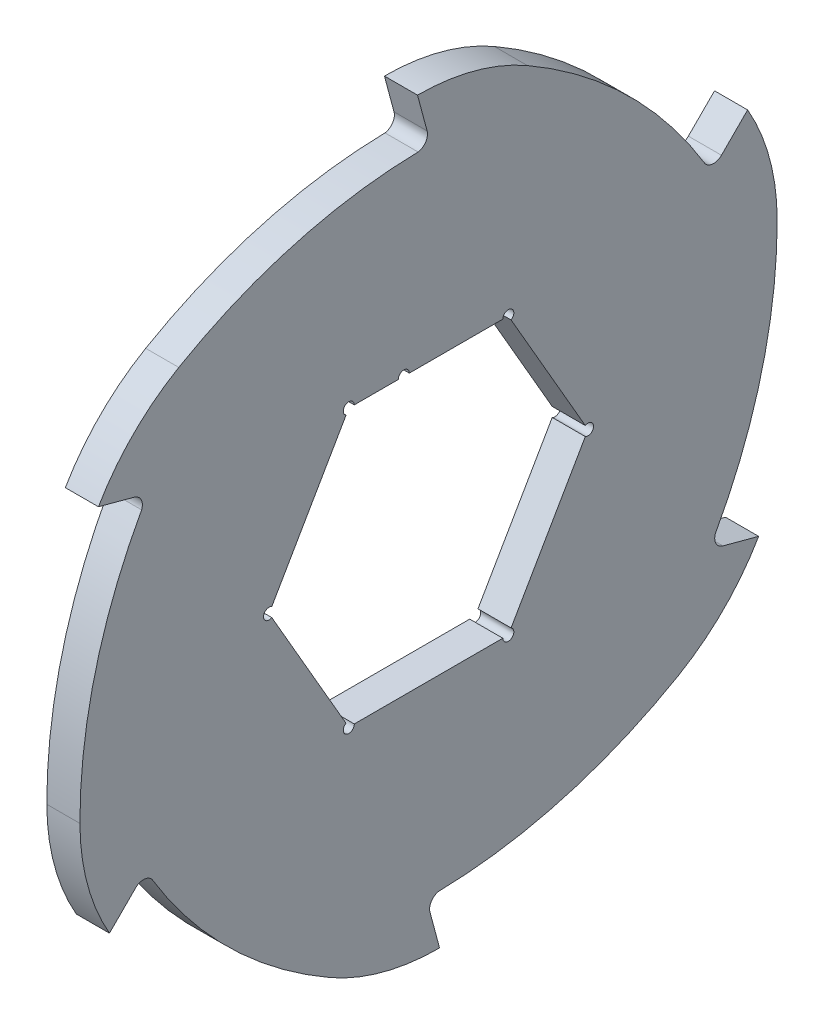
SolidWorks part; units mm, degrees
note: '?' marks a value the reader was unsure of.
material "1.0037 (S235JR)"
ref_plane "Alzado" through (0, 0, 0) normal (0, 0, 1) x (1, 0, 0)
ref_plane "Planta" through (0, 0, 0) normal (0, 1, 0) x (1, 0, 0)
ref_plane "Vista lateral" through (0, 0, 0) normal (1, 0, 0) x (0, 0, -1)
sketch "Sketch1" plane through (0, 0, 0) normal (1, 0, 0) x (0, 0, -1)
  line L0 (-56.6126, 0) -> (65.57, 0) construction
  line L1 (14.4626, 25.05) -> (-14.4626, 25.05)
  line L2 (-14.4626, 25.05) -> (-28.9252, 0)
  line L3 (-28.9252, 0) -> (-14.4626, -25.05)
  line L4 (-14.4626, -25.05) -> (14.4626, -25.05)
  line L5 (14.4626, -25.05) -> (28.9252, 0)
  line L6 (28.9252, 0) -> (14.4626, 25.05)
  circle A0 centre (0, 0) radius 25.05 construction
  circle A1 centre (0, 0) radius 59
  dimension "D2" = 118
  dimension "D1" = 50.1
  dimension "D3" = 0
extrude "Extrude1" add sketch "Sketch1" along normal mid plane 6
ref_axis "Axis1" through (-5.5, 0, 0) along (1, 0, 0)?
sketch "Sketch2" plane through (0, 0, 0) normal (1, 0, 0) x (0, 0, -1)
  line L0 (-2, 67.9618) -> (-0.2627, 61.4781)
  line L1 (0, 0) -> (0, 77.6328) construction
  line L4 (-2.1226, 58.9618) -> (0, 0) construction
  circle A0 centre (0, 0) radius 59 construction
  arc A1 (-2, 67.9618) -> (17.9271, 62.6448) centre (-2, 27.9618) cw
  arc A3 (51.2137, 29.2943) -> (-2.1226, 58.9618) centre (0, 0) ccw
  arc A4 (-0.2627, 61.4781) -> (-2.1226, 58.9618) centre (-2.1946, 60.9605) cw
  arc A5 (17.9271, 62.6448) -> (51.2137, 29.2943) centre (-26.9089, -15.3919) cw
  point P10 (-2, 67.9618)
  dimension "D2" = 40
  dimension "D4" = 2
  dimension "D3" = 9
  dimension "D6" = 90
  dimension "D1" = 15
  dimension "D5" = 2
extrude "Extrude2" add sketch "Sketch2" against normal mid plane 6
fillet "Fillet1" [suppressed] radius 0.6
pattern_circular "CirPattern1" count 6 over 360 about axis through (0, 0, 0) along (1, 0, 0) of "Extrude2", "Fillet1"
sketch "Sketch4" [suppressed] plane through (3, 0, 0) normal (1, 0, 0) x (0, 0, -1)
  circle A0 centre (0, 0) radius 67.9646 construction
  dimension "D1" = 135.9291
hole_wizard "Ø2.0 (2) Diameter Hole1" positions "Sketch5" profile "Sketch7" hole size "Ø2.0" standard "ISO" end condition up to next
sketch "Sketch5" plane through (3, 0, 0) normal (1, 0, 0) x (0, 0, -1)
  point P0 (-14.4626, 25.05)
  point P7 (14.4626, 25.05)
  point P8 (28.9252, 0)
  point P9 (14.4626, -25.05)
  point P10 (-14.4626, -25.05)
  point P11 (-28.9252, 0)
  dimension "D1" = 6
sketch "Sketch7" plane through (3, 25.05, 14.4626) normal (0, 1, 0) x (0, 0, -1)
  line L0 (0, 0) -> (0, 6)
  line L1 (0, 6) -> (1, 6)
  line L2 (1, 6) -> (1, 0)
  line L5 (1, 0) -> (0, 0)
  line L11 (0, -6.35) -> (0, 107.95) construction
  dimension "Diámetro de taladro hasta el siguiente" = 2
  dimension "Profundidad de taladro hasta el siguiente" = 6
hole_wizard "Ø2.0 (2) Diameter Hole3" positions "Sketch10" profile "Sketch11" hole size "Ø2.0" standard "ISO" end condition up to next
sketch "Sketch10" plane through (3, 0, 0) normal (1, 0, 0) x (0, 0, -1)
  line L0 (-13.4626, 25.05) -> (-4.4875, 25.05) construction
  line L1 (13.4626, 25.05) -> (-13.4626, 25.05) construction
  line L2 (-4.4875, 25.05) -> (4.4875, 25.05) construction
  line L3 (4.4875, 25.05) -> (13.4626, 25.05) construction
  point P2 (-4.4875, 25.05)
sketch "Sketch11" plane through (3, 25.05, 4.4875) normal (0, 1, 0) x (0, 0, -1)
  line L0 (0, 0) -> (0, 6)
  line L1 (0, 6) -> (1, 6)
  line L2 (1, 6) -> (1, 0)
  line L5 (1, 0) -> (0, 0)
  line L11 (0, -6.35) -> (0, 107.95) construction
  dimension "Diámetro de taladro hasta el siguiente" = 2
  dimension "Profundidad de taladro hasta el siguiente" = 6
hole_wizard "Ø2.0 (2) Diameter Hole4" [suppressed] positions "Sketch12" profile "Sketch13" hole size "Ø2.0" standard "ISO"
sketch "Sketch12" plane through (3, 0, 0) normal (1, 0, 0) x (0, 0, -1)
  line L0 (13.4626, 25.05) -> (-3.4875, 25.05) construction
  point P0 (4.9875, 25.05)
sketch "Sketch13" plane through (3, 25.05, -4.9875) normal (0, 1, 0) x (0, 0, -1)
  line L0 (0, 0) -> (0, 6)
  line L1 (0, 6) -> (1, 6)
  line L2 (1, 6) -> (1, 0)
  line L5 (1, 0) -> (0, 0)
  line L11 (0, -6.35) -> (0, 107.95) construction
  dimension "Diámetro de taladro hasta el siguiente" = 2
  dimension "Profundidad de taladro hasta el siguiente" = 6
pattern_circular "CirPattern2" [suppressed] count 1 every? 60? about axis through (-5.5, 0, 0) along (1, 0, 0)
pattern_circular "CirPattern3" [suppressed] count 1 every? 60? about axis through (-5.5, 0, 0) along (1, 0, 0)
equation "\"D1@Extrude2\"=\"D1@Extrude1\""
